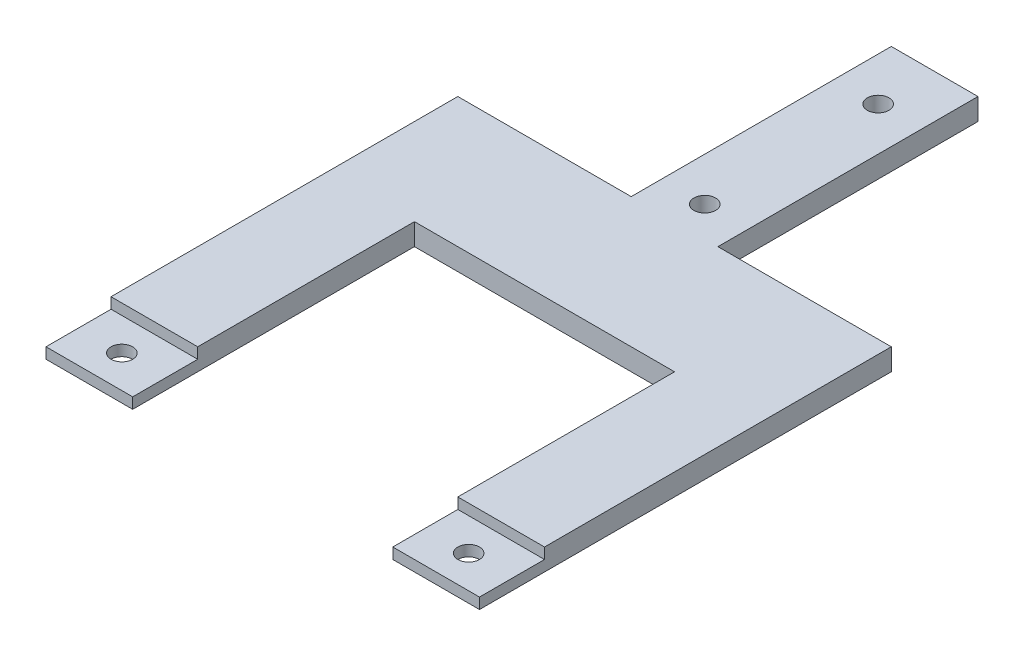
SolidWorks part; units mm, degrees
ref_plane "Front Plane" through (0, 0, 0) normal (0, 0, 1) x (1, 0, 0)
ref_plane "Top Plane" through (0, 0, 0) normal (0, 1, 0) x (1, 0, 0)
ref_plane "Right Plane" through (0, 0, 0) normal (1, 0, 0) x (0, 0, -1)
sketch "Sketch1" plane through (0, 0, 0) normal (0, 1, 0) x (1, 0, 0)
  line L1 (-15.875, 15.0812) -> (15.875, 15.0812)
  line L2 (-15.875, 15.0812) -> (-15.875, -15.0812)
  line L3 (-15.875, -15.0812) -> (15.875, -15.0812)
  line L4 (15.875, 15.0812) -> (15.875, -15.0812)
  line L5 (-9.525, -15.0812) -> (9.525, -15.0812)
  line L6 (-9.525, -15.0812) -> (-9.525, 5.5562)
  line L7 (-9.525, 5.5562) -> (9.525, 5.5562)
  line L8 (9.525, -15.0812) -> (9.525, 5.5562)
  line L9 (-3.175, 15.0813) -> (3.175, 15.0813)
  line L10 (-3.175, 15.0813) -> (-3.175, 34.1313)
  line L11 (-3.175, 34.1313) -> (3.175, 34.1313)
  line L12 (3.175, 15.0813) -> (3.175, 34.1313)
  point P4 (0, 15.0813)
  point P6 (-15.875, 0)
  point P11 (0, 5.5563)
  point P16 (0, 15.0813)
  dimension "D1" = 31.75
  dimension "D2" = 30.1625
  dimension "D3" = 6.35
  dimension "D4" = 9.525
  dimension "D5" = 6.35
  dimension "D6" = 19.05
extrude "Boss-Extrude1" add sketch "Sketch1" along normal mid plane 1.5875 contours L8 L3 L4 L1 L2 L6 L7 | L10 L9 L12 L11 region at (-9.525, 0, -14.6433)
sketch "Sketch2" plane through (0, 0.7937, 0) normal (0, 1, 0) x (1, 0, 0)
  line L0 (-9.525, -15.0812) -> (-9.525, 5.5562) construction
  line L1 (-15.875, -15.0812) -> (-9.525, -15.0812)
  line L2 (-15.875, -15.0812) -> (-15.875, -10.3187)
  line L3 (-15.875, -10.3187) -> (-9.525, -10.3187)
  line L4 (-9.525, -15.0812) -> (-9.525, -10.3187)
  line L5 (15.875, 15.0812) -> (15.875, -15.0812) construction
  line L6 (9.525, -15.0812) -> (15.875, -15.0812)
  line L7 (9.525, -15.0812) -> (9.525, -10.3187)
  line L8 (9.525, -10.3187) -> (15.875, -10.3187)
  line L9 (15.875, -15.0812) -> (15.875, -10.3187)
  dimension "D1" = 4.7625
extrude "Cut-Extrude1" cut sketch "Sketch2" against normal blind 0.7937
sketch "Sketch3" plane through (0, 0.7937, 0) normal (0, 1, 0) x (1, 0, 0)
  line L0 (-9.525, -10.3187) -> (-15.875, -10.3187) construction
  line L1 (-15.875, -10.3187) -> (-15.875, -15.0812) construction
  line L2 (0, -1000) -> (0, 49000) construction
  line L5 (-3.175, 34.1313) -> (3.175, 34.1313) construction
  circle A0 centre (-12.7, -12.7) radius 0.7937
  circle A2 centre (12.7, -12.7) radius 0.7937
  circle A4 centre (0, 17.294) radius 0.7937
  circle A5 centre (0, 29.994) radius 0.7937
  point P6 (-12.7, -10.3187)
  point P9 (-15.875, -12.7)
  dimension "D5" = 12.7
  dimension "D6" = 4.1372
  dimension "D7" = 1.5875
extrude "Cut-Extrude2" cut sketch "Sketch3" against normal up to surface (1.5875 mm away) from surface up to face at (0, -0.7937, -6.6146) starting at face at (0, 0.7937, -8.2021)
